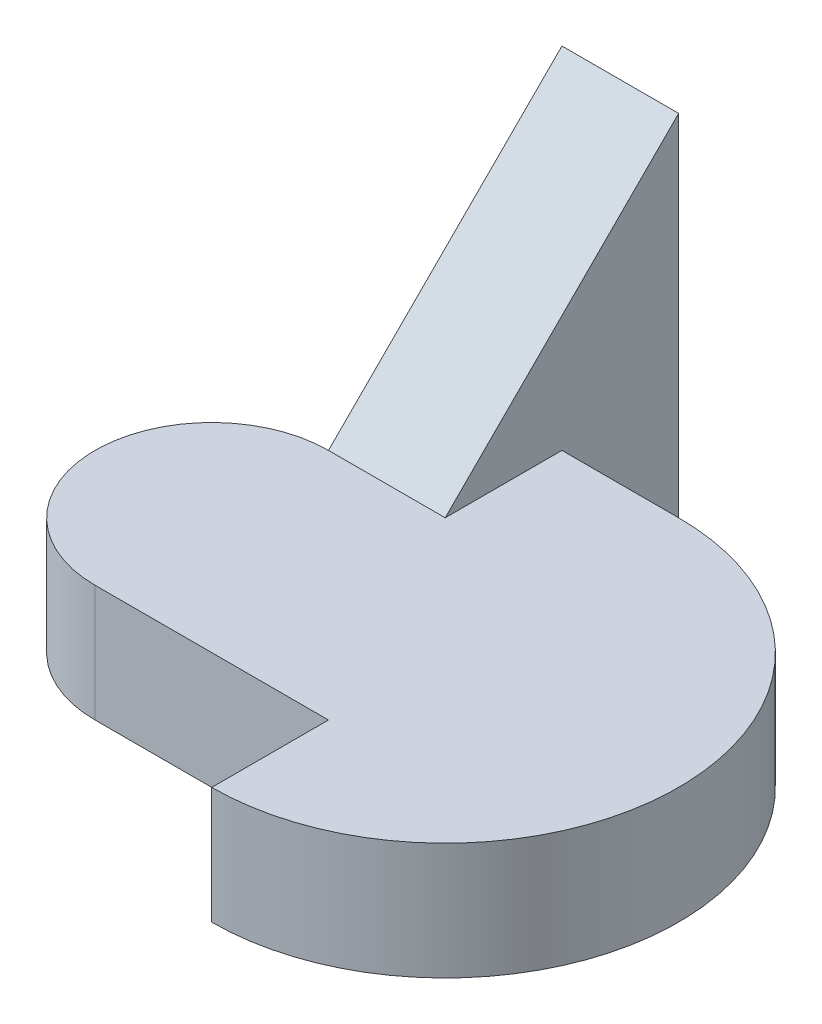
SolidWorks part; units mm, degrees
ref_plane "前基準面" through (0, 0, 0) normal (0, 0, 1) x (1, 0, 0)
ref_plane "上基準面" through (0, 0, 0) normal (0, 1, 0) x (1, 0, 0)
ref_plane "右基準面" through (0, 0, 0) normal (1, 0, 0) x (0, 0, -1)
sketch "草圖1" plane through (0, 0, 0) normal (0, 1, 0) x (1, 0, 0)
  line L0 (0, 0) -> (-10, 0) construction
  line L1 (-10, -5) -> (0, -5)
  line L2 (0, -5) -> (0, -10)
  line L3 (0, 10) -> (-5, 10)
  line L4 (-5, 10) -> (-5, 5)
  line L5 (-5, 5) -> (-10, 5)
  line L7 (-10, 5) -> (-5, 5)
  line L8 (-10, 5) -> (-10, 15)
  line L9 (-10, 15) -> (-5, 15)
  line L10 (-5, 5) -> (-5, 15)
  arc A1 (-10, 5) -> (-10, -5) centre (-10, 0) ccw
  arc A2 (0, -10) -> (0, 10) centre (0, 0) ccw
  dimension "D1" = 10
  dimension "D3" = 10
  dimension "D4" = 5
  dimension "D5" = 10
extrude "填料-伸長1" add sketch "草圖1" along normal blind 5 contours L2 A2 L3 L4 L5 A1 L1 region at (-1.1572, 0, -0.5835)
extrude "填料-伸長2" add sketch "草圖1<3>" along normal blind 15 contours L4 L10 L9 L8 L5 region at (-7.5, 0, -10)
sketch "草圖1<3>" plane through (0, 0, 0) normal (0, 1, 0) x (1, 0, 0) same geometry as "草圖1"
sketch "草圖2" plane through (-10, 0, 0) normal (-1, 0, 0) x (0, 0, 1)
  line L0 (-15, 15) -> (-5, 5)
  line L1 (-5, 5) -> (-5, 15)
  line L2 (-5, 15) -> (-15, 15)
extrude "除料-伸長1" cut sketch "草圖2" against normal blind 15
